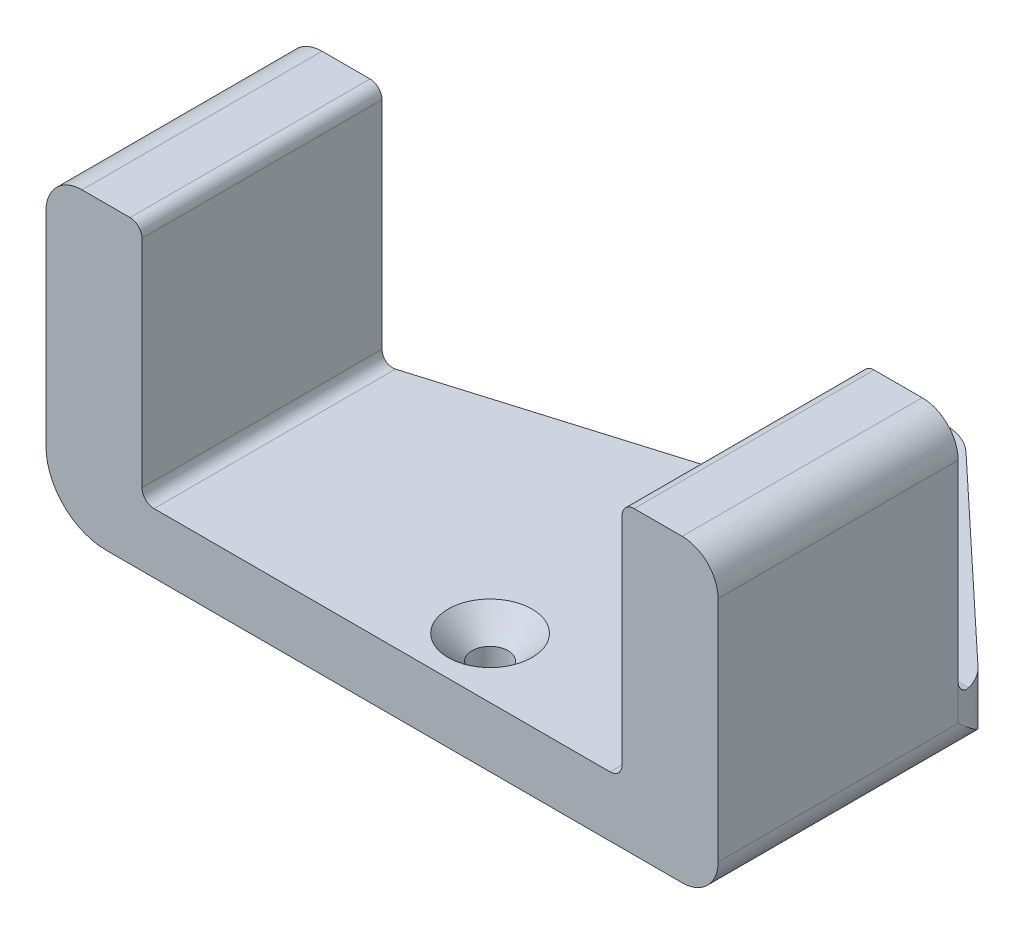
SolidWorks part; units mm, degrees
material "ABS"
ref_plane "Front" through (0, 0, 0) normal (0, 0, 1) x (1, 0, 0)
ref_plane "Top" through (0, 0, 0) normal (0, 1, 0) x (1, 0, 0)
ref_plane "Right" through (0, 0, 0) normal (1, 0, 0) x (0, 0, -1)
sketch "Esquisse1" plane through (0, 0, 0) normal (0, 0, 1) x (1, 0, 0)
  line L0 (20, 25) -> (28, 25)
  line L1 (-28, 25) -> (-20, 25)
  line L2 (-28, 25) -> (-28, 0)
  line L3 (-28, 0) -> (28, 0)
  line L4 (28, 25) -> (28, 0)
  line L6 (-20, 25) -> (-20, 5)
  line L7 (-20, 5) -> (20, 5)
  line L8 (20, 25) -> (20, 5)
  line L9 (0, -50) -> (0, 50) construction
  circle A0 centre (-24, 20) radius 0.85
  circle A1 centre (-24, 10) radius 0.85
  circle A2 centre (24, 10) radius 0.85
  circle A3 centre (24, 20) radius 0.85
  dimension "D1" = 10
  dimension "D2" = 48
  dimension "D6" = 5
  dimension "D7" = 1.7
  dimension "D9" = 4
  dimension "D3" = 40
  dimension "D4" = 5
  dimension "D5" = 5
  dimension "D8" = 56
  dimension "D10" = 8
  dimension "D11" = 25
extrude "Boss.-Extru.1" add sketch "Esquisse1" along normal blind 20
sketch "Esquisse2" plane through (0, 5, 0) normal (0, 1, 0) x (1, 0, 0)
  line L3 (-20, -20) -> (-20, 0) construction
  line L9 (-20, 0) -> (28, 0)
  line L13 (-18.8506, 0.1687) -> (1.1494, 6.1687)
  line L18 (4, 10) -> (4, 15)
  line L19 (10.7358, 17.9181) -> (26.7358, 2.9181)
  line L20 (20, 0) -> (-20, 0) construction
  line L21 (28, -20) -> (28, 0) construction
  arc A9 (1.1494, 6.1687) -> (4, 10) centre (0, 10) ccw
  arc A10 (4, 15) -> (10.7358, 17.9181) centre (8, 15) cw
  arc A11 (26.7358, 2.9181) -> (28, 0) centre (24, 0) cw
  arc A12 (-18.8506, 0.1687) -> (-20, 0) centre (-20, 4) cw
  dimension "D1" = 4
  dimension "D2" = 15
  dimension "D3" = 8
  dimension "D4" = 10
extrude "Boss.-Extru.2" add sketch "Esquisse2" against normal up to surface (5 mm away) up to face at (0, 0, 10)
sketch "Esquisse3" plane through (0, 5, 0) normal (0, 1, 0) x (1, 0, 0)
  circle A0 centre (8, 15) radius 1.5
  circle A1 centre (4, -15) radius 1.5
  dimension "D1" = 3
  dimension "D2" = 8
  dimension "D3" = 4
  dimension "D4" = 15
  dimension "D5" = 15
extrude "Enlèv. mat.-Extru.1" cut sketch "Esquisse3" against normal through all
fillet "Congé1" radius 1 5 edges at (24, 5, 0) (20, 25, 10) (-20, 25, 10) (20, 5, 10) (-20, 5, 10)
fillet "Congé2" radius 3 3 edges at (28, 0, 10) (28, 25, 10) (-28, 25, 10) tangent propagation no
chamfer "Chanfrein2" distance 2 angle 45 1 edges at (4, 5, 16.5)
fillet "Congé3" radius 5 1 edges at (-28, 0, 10)
sketch "Esquisse4" plane through (0, 0, 20) normal (0, 0, 1) x (1, 0, 0)
  line L8 (-28, 22) -> (-28, 5)
  line L9 (-23, 0) -> (25, 0)
  line L10 (28, 3) -> (28, 22)
  line L11 (25, 25) -> (21, 25)
  line L12 (20, 24) -> (20, 6)
  line L13 (19, 5) -> (-19, 5)
  line L14 (-20, 6) -> (-20, 24)
  line L15 (-21, 25) -> (-25, 25)
  line L16 (-28, 22) -> (-28, 5)
  line L17 (-23, 0) -> (25, 0)
  line L18 (28, 3) -> (28, 22)
  line L19 (25, 25) -> (21, 25)
  line L20 (20, 24) -> (20, 6)
  line L21 (19, 5) -> (-19, 5)
  line L22 (-20, 6) -> (-20, 24)
  line L23 (-21, 25) -> (-25, 25)
  arc A8 (-28, 5) -> (-23, 0) centre (-23, 5) ccw
  arc A9 (25, 0) -> (28, 3) centre (25, 3) ccw
  arc A10 (28, 22) -> (25, 25) centre (25, 22) ccw
  arc A11 (21, 25) -> (20, 24) centre (21, 24) ccw
  arc A12 (19, 5) -> (20, 6) centre (19, 6) ccw
  arc A13 (-20, 6) -> (-19, 5) centre (-19, 6) ccw
  arc A14 (-20, 24) -> (-21, 25) centre (-21, 24) ccw
  arc A15 (-25, 25) -> (-28, 22) centre (-25, 22) ccw
  arc A16 (-28, 5) -> (-23, 0) centre (-23, 5) ccw
  arc A17 (25, 0) -> (28, 3) centre (25, 3) ccw
  arc A18 (28, 22) -> (25, 25) centre (25, 22) ccw
  arc A19 (21, 25) -> (20, 24) centre (21, 24) ccw
  arc A20 (19, 5) -> (20, 6) centre (19, 6) ccw
  arc A21 (-20, 6) -> (-19, 5) centre (-19, 6) ccw
  arc A22 (-20, 24) -> (-21, 25) centre (-21, 24) ccw
  arc A23 (-25, 25) -> (-28, 22) centre (-25, 22) ccw
  dimension "D1" = 0
extrude "Boss.-Extru.3" add sketch "Esquisse4" against normal blind 0.2
